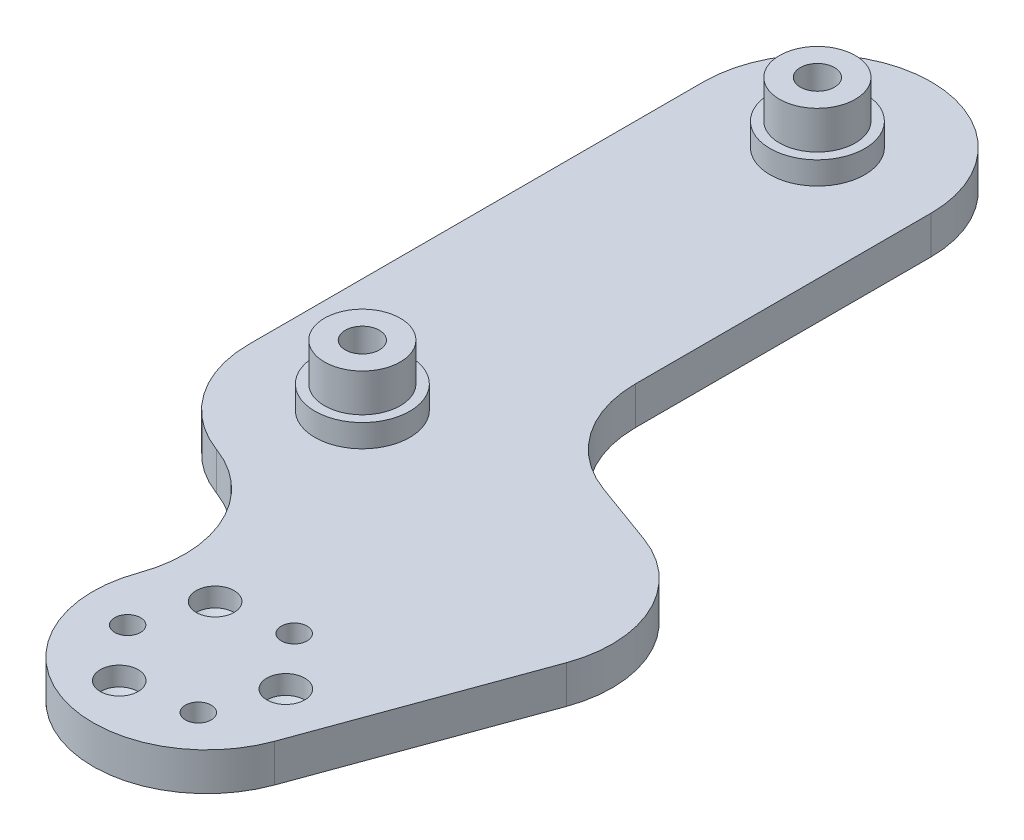
SolidWorks part; units mm, degrees
material "7075-T6 (SN)"
ref_plane "정면" through (0, 0, 0) normal (0, 0, 1) x (1, 0, 0)
ref_plane "윗면" through (0, 0, 0) normal (0, 1, 0) x (1, 0, 0)
ref_plane "우측면" through (0, 0, 0) normal (1, 0, 0) x (0, 0, -1)
sketch "스케치1" plane through (0, 0, 0) normal (0, 1, 0) x (1, 0, 0)
  line L0 (0, 0) -> (0, 60) construction
  line L1 (-15, 0) -> (-15, 60)
  line L2 (15, 0) -> (15, 60)
  arc A0 (-15, 0) -> (15, 0) centre (0, 0) ccw
  arc A1 (15, 60) -> (-15, 60) centre (0, 60) ccw
  point P3 (0, 30)
  dimension "D2" = 15
  dimension "D1" = 60
extrude "보스-돌출1" add sketch "스케치1" along normal blind 5 contours A1 L1 A0 L2
sketch "스케치2" plane through (0, 5, 0) normal (0, 1, 0) x (1, 0, 0)
  line L0 (0, 60) -> (0, 0) construction
  circle A0 centre (0, 60) radius 6.25
  circle A1 centre (0, 0) radius 6.25
  dimension "D2" = 12.5
  dimension "D3" = 12.5
  dimension "D1" = 60
extrude "보스-돌출2" add sketch "스케치2" along normal blind 3
sketch "스케치3" plane through (0, 8, 0) normal (0, 1, 0) x (1, 0, 0)
  circle A0 centre (0, 60) radius 5
  circle A1 centre (0, 0) radius 5
  dimension "D1" = 10
  dimension "D2" = 10
extrude "보스-돌출3" add sketch "스케치3" along normal blind 5
sketch "스케치4" plane through (0, 0, 0) normal (0, -1, 0) x (1, 0, 0)
  line L0 (0, -60) -> (0, 5) construction
  dimension "D1" = 65
hole_wizard "M4 육각 소켓 머리 캡 나사용 카운터보어3" positions "스케치5" profile "스케치7" counterbore size "M4" standard "ISO" end condition through all
sketch "스케치5" plane through (0, 0, 0) normal (0, -1, 0) x (-1, 0, 0)
  point P3 (0, 60)
  point P10 (0, -25)
  dimension "D1" = 85
sketch "스케치7" plane through (0, 0, -60) normal (1, 0, 0) x (0, 0, -1)
  line L0 (0, 0) -> (0, 13)
  line L1 (0, 13) -> (2.25, 13)
  line L3 (2.25, 13) -> (2.25, 4.4)
  line L4 (2.25, 4.4) -> (4, 4.4)
  line L5 (4, 4.4) -> (4, 0)
  line L7 (4, 0) -> (0, 0)
  line L11 (0, -6.35) -> (0, 107.95) construction
  dimension "관통 구멍 지름" = 4.5
  dimension "관통 구멍 깊이" = 13
  dimension "카운터보어 지름" = 8
  dimension "카운터보어 깊이" = 4.4
sketch "스케치8" plane through (0, 0, 0) normal (0, -1, 0) x (1, 0, 0)
  line L0 (0, 0) -> (28.1908, 10.2606) construction
  line L1 (15, 0) -> (15, -60) construction
  line L2 (0, 0) -> (28.1908, 10.2606) construction
  line L3 (-5.1303, 14.0954) -> (23.0605, 24.356)
  line L4 (15, -10.5031) -> (33.3211, -3.8348)
  line L5 (15, 0) -> (15, -10.5031)
  arc A1 (33.3211, -3.8348) -> (23.0605, 24.356) centre (28.1908, 10.2606) ccw
  arc A2 (15, 0) -> (-15, 0) centre (0, 0) ccw construction
  arc A3 (15, 0) -> (-5.1303, 14.0954) centre (0, 0) ccw
  point P3 (15, 5.4596)
  dimension "D3" = 15
  dimension "D1" = 110
  dimension "D2" = 30
extrude "보스-돌출4" add sketch "스케치8" against normal blind 5
sketch "스케치9" plane through (0, 0, 0) normal (0, -1, 0) x (1, 0, 0)
  line L1 (23.0605, 24.356) -> (-5.1303, 14.0954) construction
  line L8 (28.1908, 10.2606) -> (17.9302, 38.4514) construction
  line L9 (14.0954, 5.1303) -> (3.8348, 33.3211)
  line L10 (42.2862, 15.3909) -> (32.0256, 43.5817)
  arc A1 (14.0954, 5.1303) -> (42.2862, 15.3909) centre (28.1908, 10.2606) ccw
  arc A2 (32.0256, 43.5817) -> (3.8348, 33.3211) centre (17.9302, 38.4514) ccw
  point P5 (23.0605, 24.356)
  point P10 (23.0605, 24.356)
  dimension "D2" = 15
  dimension "D1" = 30
  dimension "D7" = 90
extrude "보스-돌출5" add sketch "스케치9" against normal blind 5
hole_wizard "M4 육각 소켓 머리 캡 나사용 카운터보어2" positions "스케치19" profile "스케치20" counterbore size "M4" standard "ISO" end condition through all
sketch "스케치19" plane through (0, 0, 0) normal (0, -1, 0) x (-1, 0, 0)
  point P0 (0, 0)
sketch "스케치20" plane through (0, 0, 0) normal (1, 0, 0) x (0, 0, -1)
  line L0 (0, 0) -> (0, 13)
  line L1 (0, 13) -> (2.25, 13)
  line L3 (2.25, 13) -> (2.25, 4.4)
  line L4 (2.25, 4.4) -> (4, 4.4)
  line L5 (4, 4.4) -> (4, 0)
  line L7 (4, 0) -> (0, 0)
  line L11 (0, -6.35) -> (0, 107.95) construction
  dimension "관통 구멍 지름" = 4.5
  dimension "관통 구멍 깊이" = 13
  dimension "카운터보어 지름" = 8
  dimension "카운터보어 깊이" = 4.4
sketch "스케치21" plane through (0, 0, 0) normal (0, -1, 0) x (1, 0, 0)
  line L0 (3.8348, 33.3211) -> (8.9651, 19.2257) construction
  line L1 (19.9008, 33.037) -> (11.3503, 56.5294) construction
  circle A0 centre (17.9302, 38.4514) radius 9 construction
  dimension "D1" = 18
  dimension "D2" = 25
hole_wizard "M3 육각 소켓 머리 캡 나사용 카운터보어1" positions "스케치26" profile "스케치28" counterbore size "M3" standard "ISO" end condition through all
sketch "스케치26" plane through (0, 0, 0) normal (0, -1, 0) x (-1, 0, 0)
  line L0 (-19.9008, -33.037) -> (-11.3503, -56.5294) construction
  circle A0 centre (-17.9302, -38.4514) radius 9 construction
  point P0 (-21.0084, -29.9941)
sketch "스케치28" plane through (21.0084, 0, 29.9941) normal (1, 0, 0) x (0, 0, -1)
  line L0 (0, 0) -> (0, 13)
  line L1 (0, 13) -> (1.7, 13)
  line L3 (1.7, 13) -> (1.7, 2.5)
  line L4 (1.7, 2.5) -> (3.25, 2.5)
  line L5 (3.25, 2.5) -> (3.25, 0)
  line L7 (3.25, 0) -> (0, 0)
  line L11 (0, -6.35) -> (0, 107.95) construction
  dimension "관통 구멍 지름" = 3.4
  dimension "관통 구멍 깊이" = 13
  dimension "카운터보어 지름" = 6.5
  dimension "카운터보어 깊이" = 2.5
pattern_circular "원형 패턴1" count 3 over 360 about axis through (17.9302, 5, 38.4514) along (0, -1, 0) of "M3 육각 소켓 머리 캡 나사용 카운터보어1"
hole_wizard "Ø5.0mm 맞춤핀 구멍1" positions "스케치35" profile "스케치36" hole size "Ø5.0" standard "ISO"
sketch "스케치35" plane through (0, 5, 0) normal (0, 1, 0) x (1, 0, 0)
  line L0 (19.9008, -33.037) -> (11.3503, -56.5294) construction
  circle A0 centre (17.9302, -38.4514) radius 9 construction
  point P0 (14.852, -46.9086)
sketch "스케치36" plane through (14.852, 5, 46.9086) normal (1, 0, 0) x (0, 0, 1)
  line L0 (0, 0) -> (0, 4.0022)
  line L1 (0, 4.0022) -> (2.5, 2.5)
  line L2 (2.5, 2.5) -> (2.5, 0)
  line L5 (2.5, 0) -> (0, 0)
  line L10 (0, 4.0022) -> (-2.5, 2.5) construction
  line L11 (0, -6.35) -> (0, 107.95) construction
  dimension "구멍 지름" = 5
  dimension "구멍 깊이" = 2.5
  dimension "드릴 각도" = 118
pattern_circular "원형 패턴2" count 3 over 360 about axis through (17.9302, 5, 38.4514) along (0, -1, 0) of "Ø5.0mm 맞춤핀 구멍1" reverse direction yes
fillet "필렛2" radius 15 2 edges at (15, 2.5, -10.5031) (8.9651, 2.5, 19.2257)
